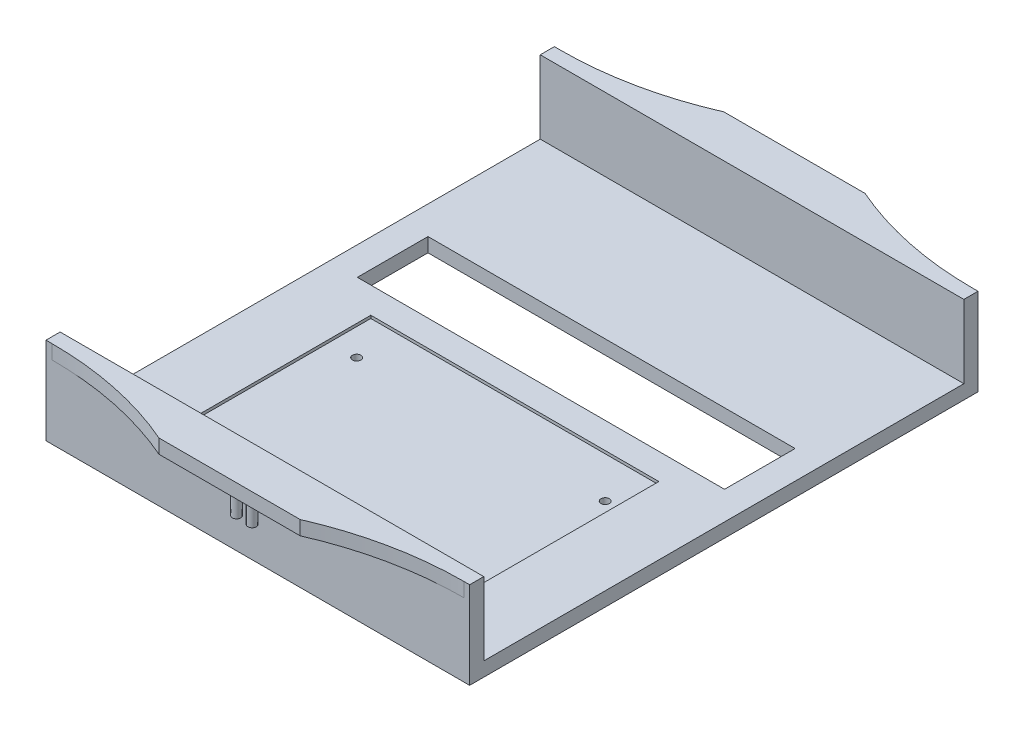
SolidWorks part; units mm, degrees
ref_plane "Front Plane" through (0, 0, 0) normal (0, 0, 1) x (1, 0, 0)
ref_plane "Top Plane" through (0, 0, 0) normal (0, 1, 0) x (1, 0, 0)
ref_plane "Right Plane" through (0, 0, 0) normal (1, 0, 0) x (0, 0, -1)
sketch "Sketch1" plane through (0, 0, 0) normal (1, 0, 0) x (0, 0, -1)
  line L7 (-180, 18.0225) -> (-180, 43.882)
  line L8 (-180, 43.882) -> (-190, 43.882)
  line L9 (-190, 43.882) -> (-190, 48.882)
  line L10 (-190, 48.882) -> (-175, 48.882)
  line L11 (-175, 48.882) -> (-175, 23.0225)
  line L12 (-180, 18.0225) -> (0, 18.0225)
  line L13 (0, 18.0225) -> (0, 43.882)
  line L14 (0, 43.882) -> (10, 43.882)
  line L15 (10, 43.882) -> (10, 48.882)
  line L16 (10, 48.882) -> (-5, 48.882)
  line L17 (-5, 48.882) -> (-5, 23.0225)
  line L18 (-5, 23.0225) -> (-175, 23.0225)
  dimension "D1" = 200
  dimension "D2" = 5
  dimension "D3" = 10
  dimension "D4" = 5
  dimension "D5" = 170
  dimension "D6" = 180
extrude "Boss-Extrude1" add sketch "Sketch1" along normal blind 150
sketch "Sketch2" plane through (0, 0, 0) normal (0, 1, 0) x (1, 0, 0)
  line L2 (50, 10) -> (0, 10)
  line L3 (150, 10) -> (0, 10) construction
  line L9 (100, 10) -> (150, 10)
  line L11 (0, -190) -> (50, -190)
  line L12 (150, -190) -> (0, -190) construction
  line L17 (150, -190) -> (100, -190)
  line L21 (0, 10) -> (0, 0)
  line L22 (0, 0) -> (50, 0)
  line L23 (50, 0) -> (50, 10)
  line L24 (100, 10) -> (100, 0)
  line L25 (100, 0) -> (150, 0)
  line L26 (150, 0) -> (150, 10)
  line L27 (0, -190) -> (0, -180)
  line L28 (0, -180) -> (50, -180)
  line L29 (50, -180) -> (50, -190)
  line L30 (100, -190) -> (100, -180)
  line L31 (100, -180) -> (150, -180)
  line L32 (150, -180) -> (150, -190)
  dimension "D1" = 50
extrude "Cut-Extrude2" cut sketch "Sketch2" along normal up to next
fillet "Fillet1" radius 120 4 edges at (50, 46.382, 180) (100, 46.382, 180) (100, 46.382, 0) (50, 46.382, 0)
sketch "Sketch4" plane through (0, 48.882, 0) normal (0, 1, 0) x (1, 0, 0)
  circle A0 centre (72.5, -185) radius 1.5
  circle A2 centre (78, -185) radius 1.5
  circle A3 centre (78, 3.5) radius 1.5
  circle A4 centre (72.5, 3.5) radius 1.5
  dimension "D2" = 3
  dimension "D5" = 2
  dimension "D6" = 2
extrude "Boss-Extrude2" add sketch "Sketch4" against normal blind 15
sketch "Sketch7" plane through (0, 33.882, 0) normal (0, -1, 0) x (1, 0, 0)
  circle A0 centre (72.5, 185) radius 1.1995
  circle A1 centre (78, 185) radius 1.2033
  circle A2 centre (72.5, -3.5) radius 1.2
  circle A3 centre (78, -3.5) radius 1.2
extrude "Cut-Extrude4" cut sketch "Sketch7" against normal up to surface (10 mm away) up to face at (78, 43.882, 186.5)
sketch "Sketch8" plane through (0, 23.0225, 0) normal (0, 1, 0) x (1, 0, 0)
  line L0 (10, -79.7494) -> (140, -79.7494)
  line L1 (10, -79.7494) -> (10, -54.7494)
  line L3 (10, -54.7494) -> (140, -54.7494)
  line L9 (140, -54.7494) -> (140, -79.7494)
  dimension "D1" = 25
  dimension "D2" = 130
extrude "Cut-Extrude5" cut sketch "Sketch8" against normal up to surface (5 mm away) up to face at (75, 18.0225, 90)
sketch "Sketch10" plane through (0, 23.0225, 0) normal (0, 1, 0) x (1, 0, 0)
  line L12 (25, -89) -> (126, -89)
  line L13 (126, -89) -> (126, -171)
  line L14 (126, -171) -> (24, -171)
  line L15 (24, -171) -> (24, -89)
  line L16 (24, -89) -> (25, -89)
  circle A0 centre (33.5, -103.5) radius 1.5
  circle A1 centre (121.5, -103.5) radius 1.5
  circle A2 centre (121.5, -166.5) radius 1.5
  circle A3 centre (33.5, -166.5) radius 1.5
  dimension "D1" = 3
extrude "Cut-Extrude6" cut sketch "Sketch10" against normal blind 1 contours L12 L13 L14 L15 L16
extrude "Cut-Extrude7" cut sketch "Sketch10<3>" against normal through all contours A1 | A0 | A3 | A2
sketch "Sketch10<3>" plane through (0, 23.0225, 0) normal (0, 1, 0) x (1, 0, 0) same geometry as "Sketch10"
fillet "Fillet2" radius 1 4 edges at (78, 43.882, -2) (72.5, 43.882, -2) (78, 43.882, 186.5) (72.5, 43.882, 186.5)
